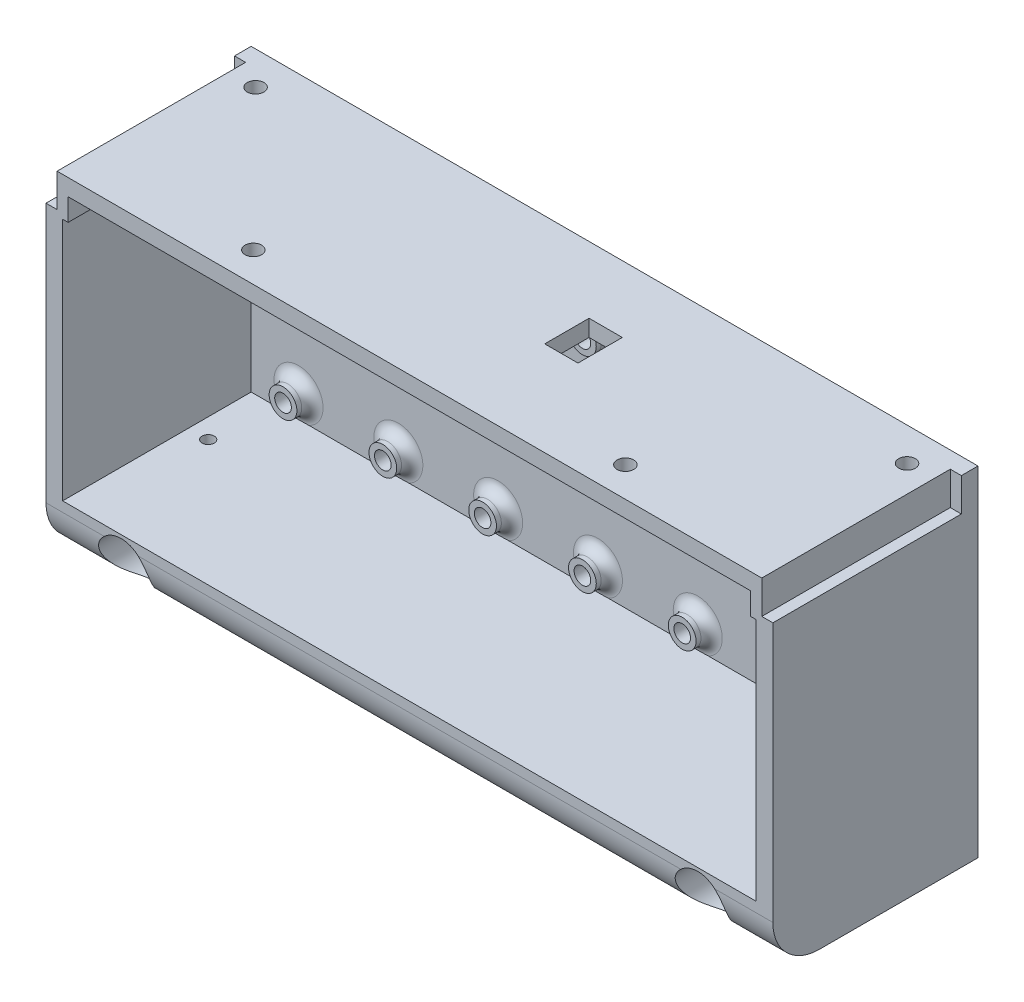
SolidWorks part; units mm, degrees
material "ABS"
ref_plane "Alzado" through (0, 0, 0) normal (0, 0, 1) x (1, 0, 0)
ref_plane "Planta" through (0, 0, 0) normal (0, 1, 0) x (1, 0, 0)
ref_plane "Vista lateral" through (0, 0, 0) normal (1, 0, 0) x (0, 0, -1)
sketch "Croquis2" plane through (0, 0, 0) normal (0, 0, 1) x (1, 0, 0)
  line L0 (0, 0) -> (131.1, 0)
  line L1 (131.1, 0) -> (131.1, -54)
  line L2 (131.1, -54) -> (0, -54)
  line L3 (0, -54) -> (0, 0)
  dimension "D1" = 131.1
  dimension "D2" = 54
extrude "Saliente-Extruir2" add sketch "Croquis2" along normal blind 3
sketch "Croquis3" plane through (0, 0, 3) normal (0, 0, 1) x (1, 0, 0)
  line L0 (0, -6) -> (2, -6)
  line L1 (0, 0) -> (0, -54) construction
  line L2 (2, -6) -> (2, 0)
  line L3 (131.1, 0) -> (0, 0) construction
  line L4 (2, 0) -> (129.1, 0)
  line L5 (129.1, 0) -> (129.1, -6)
  line L6 (129.1, -6) -> (131.1, -6)
  line L7 (131.1, -54) -> (131.1, 0) construction
  line L8 (131.1, -6) -> (131.1, -54)
  line L9 (131.1, -54) -> (0, -54)
  line L10 (0, -54) -> (0, -6)
  line L11 (65.55, 0) -> (66.55, 0)
  line L12 (65.55, 0) -> (64.55, 0)
  line L13 (64.55, 0) -> (64.55, -6)
  line L14 (66.55, 0) -> (66.55, -6)
  line L15 (64.55, -6) -> (62.55, -6)
  line L16 (62.55, -6) -> (62.55, 0)
  line L17 (66.55, -6) -> (68.55, -6)
  line L18 (68.55, -6) -> (68.55, 0)
  line L19 (3, -7) -> (128.1, -7)
  line L20 (128.1, -7) -> (128.1, -51)
  line L21 (128.1, -51) -> (3, -51)
  line L22 (3, -51) -> (3, -7)
  line L23 (62.55, 0) -> (64.55, 0)
  line L24 (66.55, 0) -> (68.55, 0)
  point P31 (130.1, -6)
  line M15 (0, 0) -> (0, -54)
  line M16 (0, -54) -> (131.1, -54)
  line M17 (131.1, -54) -> (131.1, 0)
  line M18 (131.1, 0) -> (0, 0)
  dimension "D1" = 2
  dimension "D2" = 2
  dimension "D3" = 6
  dimension "D4" = 2
  dimension "D5" = 2
  dimension "D6" = 1
  dimension "D7" = 1
  dimension "D8" = 3
  dimension "D9" = 3
  dimension "D10" = 3
  dimension "D11" = 1
extrude "Saliente-Extruir3" add sketch "Croquis3" along normal blind 34 contours L18 L17 L14 L4 L13 L15 L16 L2 L0 L6 L5 L21 L22 L19 L20 M18 M15 M16 M17 | L16 L15 L13 L4 | L17 L18 L4 L14 region at (1, -7.4179, 3) region at (63.55, -3, 3) region at (67.55, -3, 3)
sketch "Croquis4" plane through (0, -54, 0) normal (0, -1, 0) x (1, 0, 0)
  line L4 (0, 0) -> (131.1, 0)
  line L5 (131.1, 0) -> (131.1, 37)
  line L6 (131.1, 37) -> (0, 37)
  line L7 (0, 37) -> (0, 0)
  line L8 (0, 0) -> (131.1, 0)
  line L9 (131.1, 0) -> (131.1, 37)
  line L10 (131.1, 37) -> (0, 37)
  line L11 (0, 37) -> (0, 0)
  dimension "D1" = 0
extrude "Saliente-Extruir4" add sketch "Croquis4" along normal blind 7.2
sketch "Croquis5" plane through (0, 0, 37) normal (0, 0, 1) x (1, 0, 0)
  line L0 (3, -7) -> (128.1, -7) construction
  line L1 (4, -7) -> (65.55, -7)
  line L2 (4, -7) -> (4, -3)
  line L3 (4, -3) -> (65.55, -3)
  line L5 (129.1, 0) -> (2, 0) construction
  line L6 (65.55, -7) -> (65.55, 0) construction
  line L7 (129.1, 0) -> (2, 0) construction
  line L8 (127.1, -3) -> (65.55, -3)
  line L11 (127.1, -7) -> (127.1, -3)
  line L12 (65.55, -7) -> (127.1, -7)
  line M24 (3, -7) -> (128.1, -7)
  dimension "D1" = 1
  dimension "D3" = 3
extrude "Cortar-Extruir1" cut sketch "Croquis5" against normal up to vertex (34 mm away) contours L6 L3 L2 M24 | L6 L11 L8 M24 region at (34.775, -5, 37) region at (96.325, -5, 37) up to point (3, -7, 3)
sketch "Croquis6" plane through (0, -3, 0) normal (0, -1, 0) x (1, 0, 0)
  line L0 (127.1, 37) -> (4, 37) construction
  line L1 (0, 37) -> (0, 3) construction
  line L2 (131.1, 37) -> (131.1, 3) construction
  line L3 (131.1, 0) -> (0, 0) construction
  line L5 (72.95, 20) -> (78.95, 20)
  line L6 (72.95, 20) -> (72.95, 12)
  line L7 (72.95, 12) -> (78.95, 12)
  line L8 (78.95, 20) -> (78.95, 12)
  line L9 (4, 3) -> (4, 37) construction
  line L10 (4, 3) -> (127.1, 3) construction
  circle A0 centre (32, 31.6) radius 1.5
  circle A1 centre (99.1, 31.6) radius 1.5
  circle A2 centre (6.8, 6) radius 1.5
  circle A3 centre (124.3, 6) radius 1.5
  point P24 (0, 0)
  dimension "D3" = 3
  dimension "D1" = 5.4
  dimension "D2" = 32
  dimension "D4" = 32
  dimension "D5" = 6.8
  dimension "D6" = 6
  dimension "D7" = 6.8
  dimension "D8" = 68.95
  dimension "D9" = 9
  dimension "D11" = 6
  dimension "D12" = 8
extrude "Cortar-Extruir2" cut sketch "Croquis6" against normal up to next
sketch "Croquis8" plane through (0, 0, 37) normal (0, 0, 1) x (1, 0, 0)
  line L0 (65.55, -61.2) -> (65.55, -51) construction
  line L1 (131.1, -61.2) -> (0, -61.2) construction
  line L2 (128.1, -51) -> (3, -51) construction
  circle A0 centre (13.55, -56.1) radius 4.5
  circle A1 centre (117.55, -56.1) radius 4.5
  point P8 (65.55, -56.1)
  dimension "D1" = 9
  dimension "D2" = 52
extrude "Cortar-Extruir3" cut sketch "Croquis8" against normal blind 33
sketch "Croquis9" plane through (0, 0, 37) normal (0, 0, 1) x (1, 0, 0)
  circle A0 centre (13.55, -56.1) radius 2.5
  circle A1 centre (117.55, -56.1) radius 2.5
  dimension "D1" = 5
extrude "Cortar-Extruir4" cut sketch "Croquis9" against normal through all
fillet "Redondeo1" radius 8.4 1 edges at (65.55, -61.2, 37)
sketch "Croquis10" plane through (0, 0, 3) normal (0, 0, 1) x (1, 0, 0)
  line L0 (60.55, -7) -> (70.55, -7) construction
  line L1 (60.55, -7) -> (70.55, -7) construction
  circle A0 centre (65.55, -10) radius 2.5
  circle A1 centre (65.55, -10) radius 1.5
  circle A2 centre (83.55, -10) radius 1.5
  circle A3 centre (83.55, -10) radius 2.5
  circle A4 centre (101.55, -10) radius 1.5
  circle A5 centre (101.55, -10) radius 2.5
  circle A6 centre (119.55, -10) radius 1.5
  circle A7 centre (119.55, -10) radius 2.5
  circle A8 centre (83.55, -47) radius 1.5
  circle A9 centre (83.55, -47) radius 2.5
  circle A10 centre (101.55, -47) radius 1.5
  circle A11 centre (101.55, -47) radius 2.5
  circle A12 centre (119.55, -47) radius 1.5
  circle A13 centre (119.55, -47) radius 2.5
  circle A16 centre (47.55, -10) radius 2.5
  circle A17 centre (47.55, -10) radius 1.5
  circle A18 centre (29.55, -10) radius 2.5
  circle A19 centre (29.55, -10) radius 1.5
  circle A20 centre (11.55, -10) radius 2.5
  circle A21 centre (11.55, -10) radius 1.5
  circle A22 centre (47.55, -47) radius 2.5
  circle A23 centre (47.55, -47) radius 1.5
  circle A24 centre (29.55, -47) radius 2.5
  circle A25 centre (29.55, -47) radius 1.5
  circle A26 centre (11.55, -47) radius 2.5
  circle A27 centre (11.55, -47) radius 1.5
  circle A28 centre (65.55, -47) radius 2.5
  circle A29 centre (65.55, -47) radius 1.5
  circle A30 centre (65.55, -47) radius 2.5 [skipped]
  circle A31 centre (65.55, -47) radius 1.5 [skipped]
  point P5 (65.55, -7)
  dimension "D1" = 5
  dimension "D3" = 3
  dimension "D2" = 3
  dimension "D4" = 4
  dimension "D5" = 2
  dimension "D6" = 4
  dimension "D7" = 2
extrude "Saliente-Extruir5" add sketch "Croquis10" along normal blind 2.8
fillet "Redondeo2" radius 1.92 14 edges at (9.05, -47, 3) (27.05, -47, 3) (45.05, -47, 3) (63.05, -47, 3) (81.05, -47, 3) (99.05, -47, 3) (117.05, -47, 3) (117.05, -10, 3) (99.05, -10, 3) (81.05, -10, 3) (63.05, -10, 3) (45.05, -10, 3) (27.05, -10, 3) (9.05, -10, 3)
sketch "Croquis11" plane through (0, -61.2, 0) normal (0, -1, 0) x (1, 0, 0)
  line L0 (0, 28.6) -> (0, 0) construction
  line L1 (0, 0) -> (131.1, 0) construction
  line L2 (65.55, 0) -> (65.55, 28.6) construction
  line L3 (131.1, 28.6) -> (0, 28.6) construction
  circle A0 centre (6.55, 14.3) radius 1.1
  circle A1 centre (124.55, 14.3) radius 1.1
  dimension "D3" = 2.2
  dimension "D1" = 6.55
  dimension "D2" = 14.3
extrude "Cortar-Extruir5" cut sketch "Croquis11" against normal up to next
